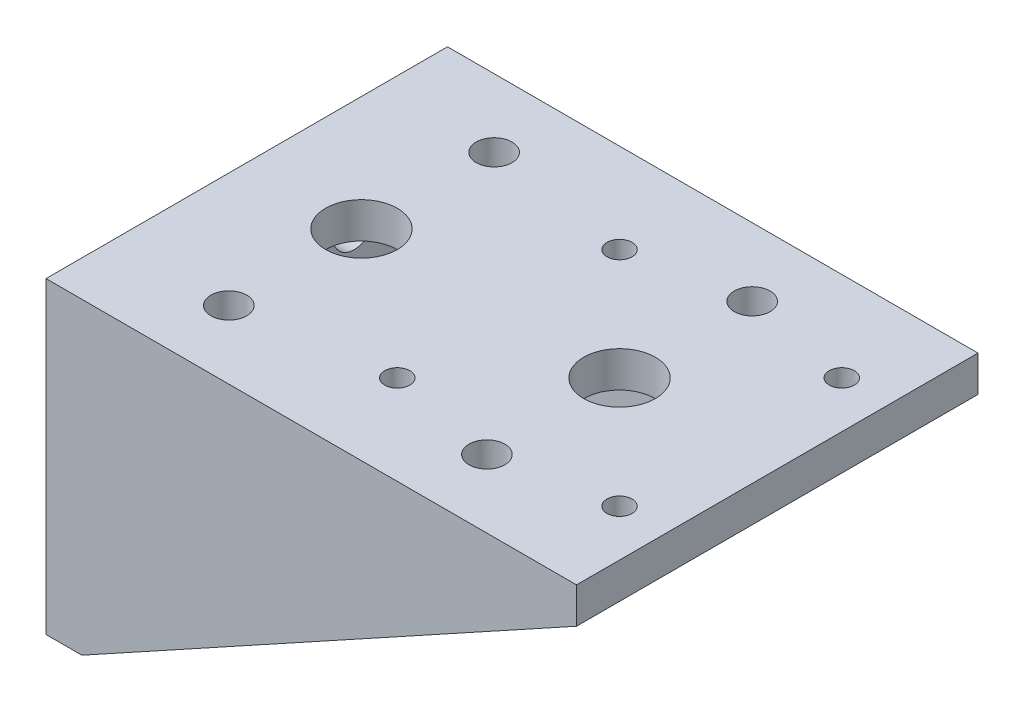
SolidWorks part; units mm, degrees
ref_plane "Спереди" through (0, 0, 0) normal (0, 0, 1) x (1, 0, 0)
ref_plane "Сверху" through (0, 0, 0) normal (0, 1, 0) x (1, 0, 0)
ref_plane "Справа" through (0, 0, 0) normal (1, 0, 0) x (0, 0, -1)
sketch "Эскиз1" plane through (0, 0, 0) normal (0, 1, 0) x (1, 0, 0)
  line L0 (0, 28) -> (74, 28) construction
  line L1 (0, 0) -> (74, 0)
  line L2 (0, 0) -> (0, 56)
  line L3 (0, 56) -> (74, 56)
  line L4 (74, 0) -> (74, 56)
  line L5 (52, 46.5) -> (52, 9.5) construction
  line L6 (30, 56) -> (30, 0) construction
  line L7 (16, 46.5) -> (16, 9.5) construction
  circle A0 centre (16, 46.5) radius 2.5
  circle A1 centre (16, 9.5) radius 2.5
  circle A2 centre (52, 46.5) radius 2.5
  circle A3 centre (52, 9.5) radius 2.5
  circle A4 centre (52, 28) radius 5
  circle A5 centre (67.5, 12.5) radius 1.75
  circle A6 centre (67.5, 43.5) radius 1.75
  circle A7 centre (36.5, 43.5) radius 1.75
  circle A8 centre (36.5, 12.5) radius 1.75
  circle A9 centre (16, 28) radius 5
  dimension "D3" = 5
  dimension "D4" = 5
  dimension "D7" = 5
  dimension "D8" = 5
  dimension "D11" = 10
  dimension "D14" = 3.5
  dimension "D17" = 10
  dimension "D1" = 56
  dimension "D2" = 74
  dimension "D5" = 37
  dimension "D6" = 16
  dimension "D9" = 37
  dimension "D10" = 22
  dimension "D12" = 44
  dimension "D13" = 30
  dimension "D15" = 31
  dimension "D16" = 31
extrude "Бобышка-Вытянуть1" add sketch "Эскиз1" along normal blind 5
sketch "Эскиз2" plane through (0, 0, 0) normal (0, -1, 0) x (-1, 0, 0)
  line L0 (-74, 0) -> (0, 0)
  line L1 (0, 0) -> (0, 56)
  line L2 (0, 56) -> (-74, 56)
  line L3 (-74, 56) -> (-74, 51)
  line L4 (-74, 0) -> (-74, 56) construction
  line L5 (-74, 51) -> (-5, 51)
  line L6 (-5, 51) -> (-5, 5)
  line L7 (-5, 5) -> (-74, 5)
  line L8 (-74, 5) -> (-74, 0)
  dimension "D1" = 5
  dimension "D2" = 5
  dimension "D3" = 5
extrude "Бобышка-Вытянуть2" add sketch "Эскиз2" along normal blind 38
sketch "Эскиз3" plane through (0, 0, 0) normal (0, 0, 1) x (1, 0, 0)
  line L0 (5, -38) -> (74, 0)
  line L1 (74, -38) -> (0, -38) construction
  line L2 (74, 5) -> (74, -38) construction
  line L3 (74, 0) -> (74, -38)
  line L4 (74, -38) -> (5, -38)
  dimension "D1" = 5
  dimension "D2" = 5
extrude "Вырез-Вытянуть1" cut sketch "Эскиз3" against normal up to surface (56 mm away) up to face at (37, -16.5, -56)
sketch "Эскиз4" plane through (0, 0, 0) normal (-1, 0, 0) x (0, 0, 1)
  line L0 (-28, -38) -> (-28, 5) construction
  line L3 (0, -15) -> (-56, -15) construction
  line L6 (-56, 5) -> (0, 5) construction
  circle A0 centre (-18, -25) radius 3
  circle A1 centre (-18, -5) radius 3
  circle A2 centre (-38, -5) radius 3
  circle A3 centre (-38, -25) radius 3
  dimension "D1" = 6
  dimension "D2" = 20
  dimension "D3" = 20
  dimension "D4" = 20
extrude "Вырез-Вытянуть2" cut sketch "Эскиз4" against normal up to surface (5 mm away) up to face at (5, -19, -28)
sketch "Эскиз6" plane through (0, 5, 0) normal (0, 1, 0) x (1, 0, 0)
  line L0 (16, 44) -> (16, 12) construction
  circle A0 centre (16, 46.5) radius 2.5 construction
  circle A1 centre (16, 9.5) radius 2.5 construction
sketch "Эскиз7" plane through (0, 5, 0) normal (0, 1, 0) x (1, 0, 0)
  line L0 (52, 44) -> (52, 12) construction
  circle A0 centre (52, 46.5) radius 2.5 construction
  circle A1 centre (52, 9.5) radius 2.5 construction
